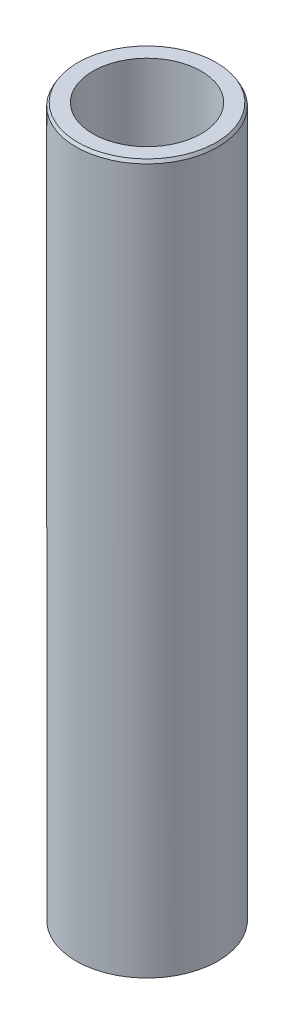
SolidWorks part; units mm, degrees
ref_plane "Front Plane" through (0, 0, 0) normal (0, 0, 1) x (1, 0, 0)
ref_plane "Top Plane" through (0, 0, 0) normal (0, 1, 0) x (1, 0, 0)
ref_plane "Right Plane" through (0, 0, 0) normal (1, 0, 0) x (0, 0, -1)
sketch "Sketch1" plane through (0, 0, 0) normal (0, 1, 0) x (1, 0, 0)
  circle A0 centre (0, 0) radius 60
  dimension "SHAFT_OD" = 120
extrude "Boss-Extrude1" add sketch "Sketch1" along normal blind 600
sketch "Sketch2" plane through (0, 0, 0) normal (0, 1, 0) x (1, 0, 0)
  circle A0 centre (0, 0) radius 45.83
  dimension "BORE_D" = 91.6601
extrude "Cut-Extrude1" cut sketch "Sketch2" along normal through all
chamfer "Chamfer1" distance 2.6048 angle 30 2 edges at (0, 600, 60) (0, 0, 60) first distance on face at (0, 600, 60) first distance on face at (0, 0, 45.83)
